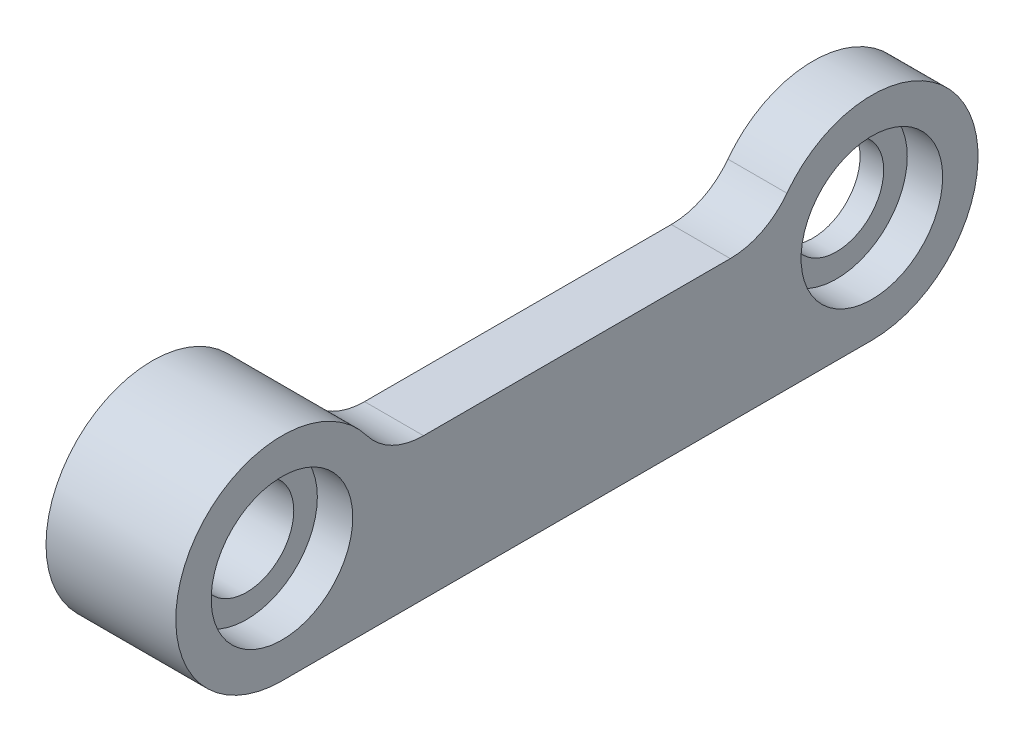
SolidWorks part; units mm, degrees
ref_plane "前视基准面" through (0, 0, 0) normal (0, 0, 1) x (1, 0, 0)
ref_plane "上视基准面" through (0, 0, 0) normal (0, 1, 0) x (1, 0, 0)
ref_plane "右视基准面" through (0, 0, 0) normal (1, 0, 0) x (0, 0, -1)
other "Configuration Table"
sketch "草图1" plane through (0, 0, 0) normal (1, 0, 0) x (0, 0, -1)
  line L1 (0, 0) -> (25, 0)
  line L2 (0, 0) -> (0, -6)
  line L3 (0, -6) -> (25, -6)
  line L4 (25, 0) -> (25, -6)
  circle A0 centre (0, -1.5) radius 4.5
  circle A1 centre (25, -1.5) radius 4.5
  circle A2 centre (0, -1.5) radius 2
  circle A3 centre (25, -1.5) radius 2
  dimension "D1" = 9
  dimension "D2" = 9
  dimension "D4" = 4
  dimension "D3" = 6
  dimension "D5" = 25
extrude "凸台-拉伸1" add sketch "草图1" along normal blind 2.5 contours A0 | L1 L4 L3 L2 | A1
extrude "凸台-拉伸3" add sketch "草图1<5>" against normal blind 3 contours A0
sketch "草图1<5>" plane through (0, 0, 0) normal (1, 0, 0) x (0, 0, -1) same geometry as "草图1"
extrude "切除-拉伸2" cut sketch "草图1<4>" along normal through all both and the other way through all contours L2 A2 | L2 A2 | L4 A3 L1 | L1 A3 L4 region at (0, -1.3854, 0.7577) region at (0, -1.6324, -0.8755) region at (0, -1.3854, -25.7577) region at (0, -1.6324, -24.1245)
sketch "草图1<4>" plane through (0, 0, 0) normal (1, 0, 0) x (0, 0, -1) same geometry as "草图1"
fillet "圆角1" radius 3 2 edges at (1.25, 0, -20.7574) (1.25, 0, -4.2426)
sketch "草图2" plane through (2.5, 0, 0) normal (1, 0, 0) x (0, 0, -1)
  circle A0 centre (0, -1.5) radius 3
  circle A1 centre (25, -1.5) radius 3
  dimension "D1" = 6
extrude "切除-拉伸3" cut sketch "草图2" against normal blind 1.5
